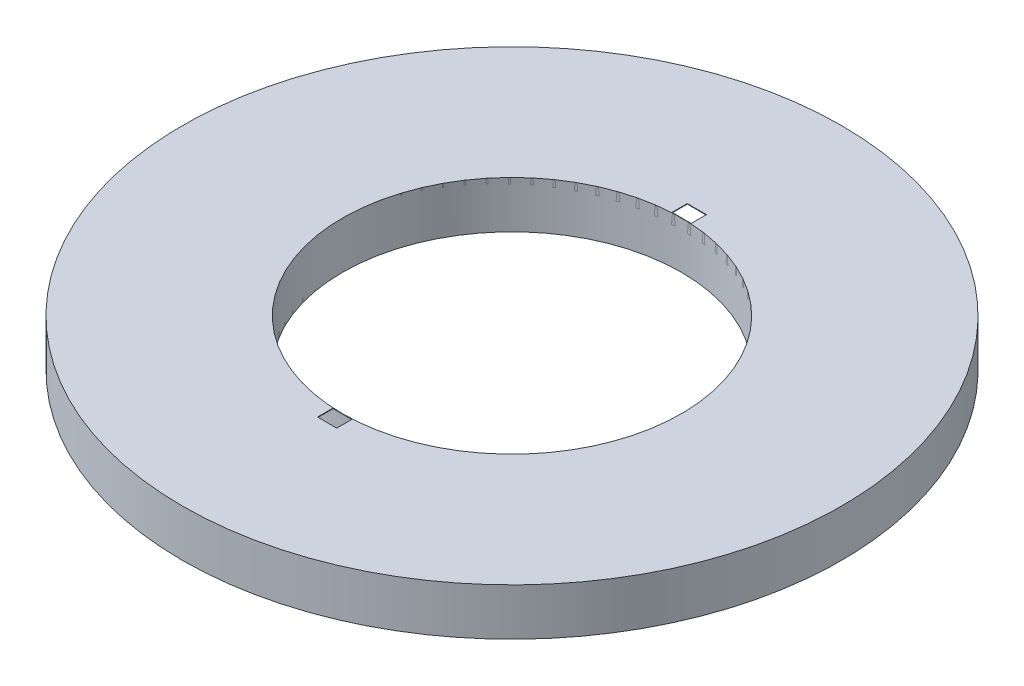
SolidWorks part; units mm, degrees
material "1345 Alloy"
ref_plane "Front Plane" through (0, 0, 0) normal (0, 0, 1) x (1, 0, 0)
ref_plane "Top Plane" through (0, 0, 0) normal (0, 1, 0) x (1, 0, 0)
ref_plane "Right Plane" through (0, 0, 0) normal (1, 0, 0) x (0, 0, -1)
sketch "Sketch1" plane through (0, 0, 0) normal (0, 1, 0) x (1, 0, 0)
  circle A0 centre (0, 0) radius 1750
extrude "Boss-Extrude1" add sketch "Sketch1" along normal blind 500
sketch "Sketch2" plane through (0, 500, 0) normal (0, 1, 0) x (1, 0, 0)
  circle A0 centre (0, 0) radius 900
extrude "Cut-Extrude2" cut sketch "Sketch2" against normal blind 300
sketch "Sketch3" plane through (0, 0, 0) normal (0, -1, 0) x (1, 0, 0)
  circle A0 centre (0, 0) radius 600
extrude "Cut-Extrude3" cut sketch "Sketch3" against normal blind 300
sketch "Sketch4" plane through (0, 0, 0) normal (0, -1, 0) x (-1, 0, 0)
  circle A0 centre (0, 0) radius 900.75
  circle A1 centre (0, 0) radius 1748.5
extrude "Cut-Extrude5" cut sketch "Sketch4" against normal blind 497
sketch "Sketch5" plane through (0, 0, 0) normal (0, 0, 1) x (1, 0, 0)
  line L0 (0, 0) -> (0, 250)
  line L1 (0, 250) -> (1750, 250)
  line L2 (1750, 0) -> (1750, 500) construction
  line L3 (1750, 250) -> (1750, 0)
  line L4 (1750, 0) -> (-1750, 0)
  line L5 (-1750, 0) -> (-1750, 250)
  line L6 (-1750, 500) -> (-1750, 0) construction
  line L7 (-1750, 250) -> (0, 250)
extrude "Cut-Extrude6" cut sketch "Sketch5" against normal through all both and the other way through all contours L7 L5 L4 L0 | L4 L3 L1 L0 region at (-875, 125, 0) region at (875, 125, 0)
sketch "Sketch6" plane through (0, 497, 0) normal (0, -1, 0) x (1, 0, 0)
  line L0 (0, 900.75) -> (51, 900.75)
  line L1 (51, 900.75) -> (51, 981.75)
  line L2 (51, 981.75) -> (-51, 981.75)
  line L3 (-51, 981.75) -> (-51, 900.75)
  line L4 (-51, 900.75) -> (0, 900.75)
  circle A0 centre (0, 0) radius 900.75 construction
  circle A1 centre (0, 0) radius 900.75 construction
extrude "Cut-Extrude7" cut sketch "Sketch6" against normal blind 10
pattern_circular "CirPattern1" count 2 every 180 about axis through (0, 497, 0) along (0, -1, 0) of "Cut-Extrude7"
